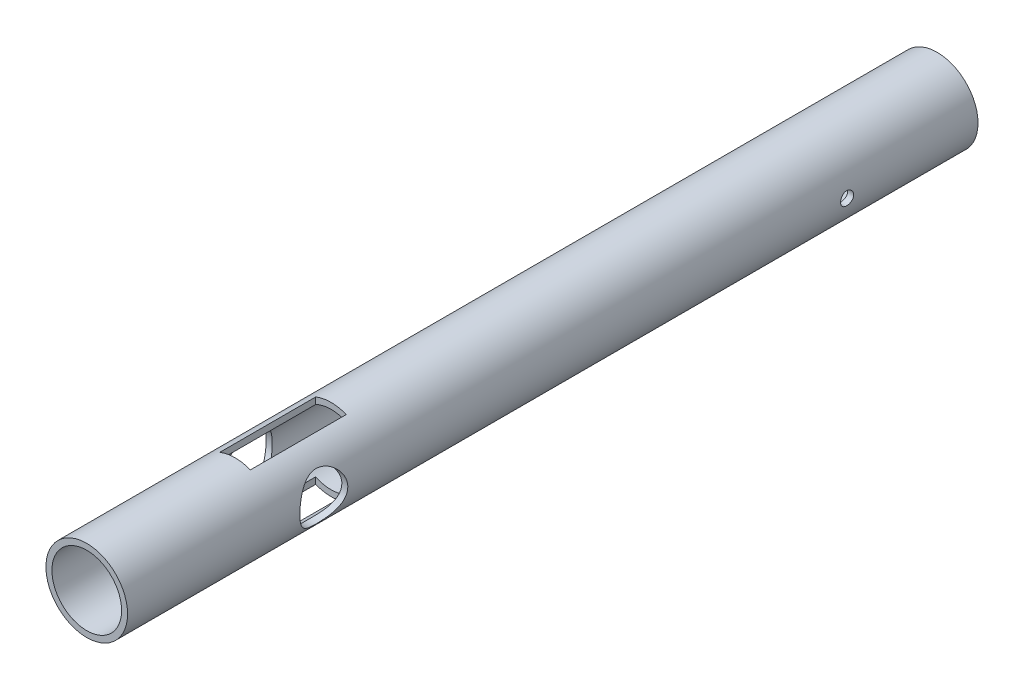
SolidWorks part; units mm, degrees
material "6061-T4 (SS)"
ref_plane "Front" through (0, 0, 0) normal (0, 0, 1) x (1, 0, 0)
ref_plane "Top" through (0, 0, 0) normal (0, 1, 0) x (1, 0, 0)
ref_plane "Right" through (0, 0, 0) normal (1, 0, 0) x (0, 0, -1)
sketch "Sketch1" plane through (0, 0, 0) normal (0, 0, 1) x (1, 0, 0)
  circle A0 centre (0, 0) radius 9.36
  circle A1 centre (0, 0) radius 7.99
extrude "Extrude1" add sketch "Sketch1" along normal blind 195
sketch "Sketch2" plane through (0, 0, 0) normal (1, 0, 0) x (0, 0, -1)
  line L0 (-30, -47.5362) -> (-30, 39.1475) construction
  line L1 (0, -9.36) -> (0, 9.36) construction
  line L2 (-150, -93.5027) -> (-150, 51.4365) construction
  circle A0 centre (-30, 0) radius 1.5
  circle A1 centre (-150, 0) radius 5.5
  dimension "D2" = 150
  dimension "D1" = 30
extrude "Extrude2" cut sketch "Sketch2" against normal through all and the other way through all
sketch "Sketch3" plane through (0, 0, 0) normal (0, 1, 0) x (1, 0, 0)
  line L0 (-54.8402, -150) -> (72.4613, -150) construction
  line L1 (7.99, 0) -> (-7.99, 0) construction
  line L2 (-44.3384, -139) -> (38.4408, -139) construction
  line L3 (-76.6388, -161) -> (67.6466, -161) construction
  line L4 (3.5, -160.8387) -> (3.5, -87.3966) construction
  line L5 (0, -179.9469) -> (0, -88.7091) construction
  line L6 (-3.5, -169.4108) -> (-3.5, -98.3485) construction
  line L8 (-3.5, -139) -> (3.5, -139)
  line L9 (-3.5, -139) -> (-3.5, -161)
  line L10 (-3.5, -161) -> (3.5, -161)
  line L11 (3.5, -139) -> (3.5, -161)
  dimension "D1" = 150
  dimension "D2" = 11
  dimension "D3" = 22
  dimension "D4" = 3.5
  dimension "D5" = 7
extrude "Extrude3" cut sketch "Sketch3" against normal blind 25 and the other way blind 25
